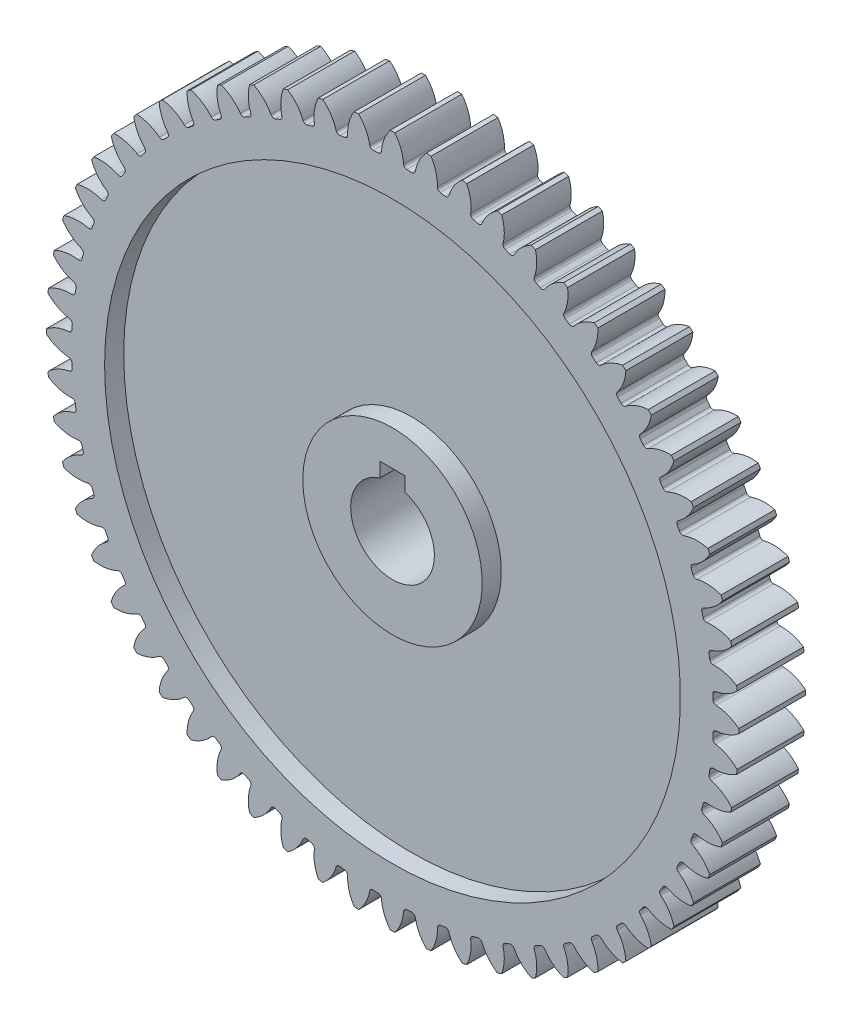
SolidWorks part; units mm, degrees
ref_plane "Front Plane" through (0, 0, 0) normal (0, 0, 1) x (1, 0, 0)
ref_plane "Top Plane" through (0, 0, 0) normal (0, 1, 0) x (1, 0, 0)
ref_plane "Right Plane" through (0, 0, 0) normal (1, 0, 0) x (0, 0, -1)
sketch "Sketch1" plane through (0, 0, 0) normal (1, 0, 0) x (0, 0, -1)
  line L0 (-7.112, 0) -> (-7.112, 32.8359)
  line L1 (-7.112, 32.8359) -> (-0.762, 32.8359)
  line L2 (-0.762, 32.8359) -> (-0.762, 8.509)
  line L3 (-0.762, 8.509) -> (7.112, 8.509)
  line L4 (7.112, 8.509) -> (7.112, 0)
  line L5 (7.112, 0) -> (-7.112, 0) construction
  line L6 (-7.112, 3.9687) -> (7.112, 3.9687)
  point P9 (-7.112, 27.305)
  dimension "OD" = 65.6717
  dimension "Face Width" = 6.35
  dimension "Hub Width" = 7.874
  dimension "Hub Diameter" = 17.018
  dimension "For Shaft Diameter" = 7.9375
  dimension "Overall Width" = 14.224
  dimension "Under Cut Diameter" = 54.61
sketch "Sketch2" plane through (0, 0, 0) normal (0, 0, 1) x (1, 0, 0)
  line L0 (-1.3192, 30.3985) -> (-0.432, 32.8359)
  line L1 (-0.432, 32.8359) -> (0.432, 32.8359)
  line L2 (0.432, 32.8359) -> (1.3192, 30.3985)
  line L3 (0, 32.8359) -> (0, 0) construction
  line L4 (0, 0) -> (-1.7185, 32.7908) construction
  line L5 (0, 0) -> (1.7185, 32.7908) construction
  line L6 (-4.4894, 30.0941) -> (-3.862, 32.6108)
  line L7 (-3.862, 32.6108) -> (-3.0026, 32.7011)
  line L8 (-3.0026, 32.7011) -> (-1.8656, 30.3698)
  line L9 (-3.4323, 32.656) -> (0, 0) construction
  line L11 (-0.432, 32.8359) -> (0, 32.8359) construction
  line L12 (-0.8312, 31.7391) -> (0.8312, 31.7391) construction
  circle A0 centre (0, 0) radius 31.75 construction
  circle A2 centre (0, 0) radius 32.8359
  circle A3 centre (0, 0) radius 30.4271
  arc A5 (-0.216, 32.8359) -> (-1.0661, 30.4084) centre (2.8289, 30.407) ccw
  arc A6 (1.0661, 30.4084) -> (0.216, 32.8359) centre (-2.8289, 30.407) ccw
  arc A7 (-2.1183, 30.3533) -> (-3.2174, 32.6786) centre (-5.9918, 29.9447) ccw
  arc A8 (-0.8312, 31.7391) -> (0.8312, 31.7391) centre (0, 0) cw
  point P3 (0, 31.75)
  point P5 (3.3188, 31.5761)
  point P6 (27.4963, -15.875)
  point P9 (6.6012, 31.0562)
  point P10 (9.8113, 30.196)
  point P11 (12.9139, 29.0051)
  point P12 (15.875, 27.4963)
  point P13 (18.6622, 25.6863)
  point P14 (21.2449, 23.5948)
  point P15 (23.5948, 21.2449)
  point P16 (25.6863, 18.6622)
  point P17 (27.4963, 15.875)
  point P18 (29.0051, 12.9139)
  point P19 (30.196, 9.8113)
  point P20 (31.0562, 6.6012)
  point P21 (31.5761, 3.3188)
  point P22 (31.75, 0)
  point P23 (31.5761, -3.3188)
  point P24 (31.0562, -6.6012)
  point P25 (30.196, -9.8113)
  point P26 (29.0051, -12.9139)
  point P27 (25.6863, -18.6622)
  point P28 (23.5948, -21.2449)
  point P29 (21.2449, -23.5948)
  point P30 (18.6622, -25.6863)
  point P31 (0, 0)
  point P55 (15.875, -27.4963)
  point P56 (12.9139, -29.0051)
  point P57 (9.8113, -30.196)
  point P58 (6.6012, -31.0562)
  point P59 (3.3188, -31.5761)
  point P61 (0, -31.75)
  point P62 (-3.3188, -31.5761)
  point P63 (-6.6012, -31.0562)
  point P64 (-9.8113, -30.196)
  point P65 (-12.9139, -29.0051)
  point P66 (-15.875, -27.4963)
  point P67 (-18.6622, -25.6863)
  point P68 (-21.2449, -23.5948)
  point P69 (-23.5948, -21.2449)
  point P70 (-25.6863, -18.6622)
  point P71 (-27.4963, -15.875)
  point P72 (-29.0051, -12.9139)
  point P73 (-30.196, -9.8113)
  point P74 (-31.0562, -6.6012)
  point P75 (-31.5761, -3.3188)
  point P76 (-31.75, 0)
  point P77 (-31.5761, 3.3188)
  point P78 (-31.0562, 6.6012)
  point P79 (-30.196, 9.8113)
  point P80 (-29.0051, 12.9139)
  point P81 (-27.4963, 15.875)
  point P82 (-25.6863, 18.6622)
  point P83 (-23.5948, 21.2449)
  point P84 (-21.2449, 23.5948)
  point P85 (-18.6622, 25.6863)
  point P86 (-15.875, 27.4963)
  point P87 (-12.9139, 29.0051)
  point P88 (-9.8113, 30.196)
  point P89 (-6.6012, 31.0562)
  point P90 (-3.3188, 31.5761)
  dimension "Gear Pitch Diameter" = 63.5
  dimension "Pressure Angle" = 20
  dimension "Addendum" = 1.0858
  dimension "Dedendum" = 1.3229
  dimension "D1" = 6
  dimension "D2" = 1.6624
  dimension "Number of Teeth" = 60
sketch "Sketch3" plane through (0, 0, 0) normal (1, 0, 0) x (0, 0, -1)
  line L0 (-7.112, 32.8359) -> (-0.762, 32.8359) construction
  line L1 (7.112, 8.509) -> (7.112, 0) construction
  line L2 (-0.762, 8.509) -> (7.112, 8.509) construction
  line L3 (-0.762, 32.8359) -> (-0.762, 8.509) construction
  line L4 (-7.112, 0) -> (-7.112, 32.8359) construction
  line L5 (-7.112, 3.9687) -> (7.112, 3.9687) construction
  line L6 (-7.112, 32.8359) -> (-0.762, 32.8359)
  line L7 (7.112, 8.509) -> (7.112, 3.9687)
  line L8 (-7.112, 8.509) -> (-5.2977, 8.509)
  line L9 (-0.762, 32.8359) -> (-0.762, 27.305)
  line L10 (-7.112, 3.9687) -> (-7.112, 8.509)
  line L11 (-7.112, 3.9687) -> (7.112, 3.9687)
  line L12 (-7.112, 27.305) -> (-5.2977, 27.305)
  line L13 (-5.2977, 27.305) -> (-5.2977, 8.509)
  line L14 (-0.762, 27.305) -> (-2.5763, 27.305)
  line L15 (-2.5763, 27.305) -> (-2.5763, 8.509)
  line L16 (-2.5763, 8.509) -> (7.112, 8.509)
  line L17 (-7.112, 27.305) -> (-7.112, 32.8359)
  dimension "D1" = 1.8143
revolve "Revolve1" add sketch "Sketch3" angle 360 about L5
sketch "Sketch4" plane through (0, 0, 7.112) normal (0, 0, 1) x (1, 0, 0)
  arc A1 (-0.216, 32.8358) -> (-1.0661, 30.4084) centre (2.8289, 30.407) ccw construction
  arc A2 (-2.1183, 30.3533) -> (-3.2174, 32.6786) centre (-5.9918, 29.9447) ccw construction
  arc A3 (-0.2166, 32.8351) -> (-1.0558, 30.6908) centre (2.8289, 30.407) ccw
  arc A4 (-2.1581, 30.633) -> (-3.2168, 32.6779) centre (-5.9918, 29.9447) ccw
  circle A5 centre (0, 0) radius 32.8359 construction
  arc A6 (-0.2166, 32.8351) -> (-3.2168, 32.6779) centre (0, 0) ccw
  circle A7 centre (0, 0) radius 30.4271 construction
  arc A8 (-1.3582, 30.3968) -> (-1.8265, 30.3722) centre (0, 0) ccw
  arc A9 (-2.1581, 30.633) -> (-1.8265, 30.3722) centre (-1.8456, 30.6891) ccw
  arc A10 (-1.3582, 30.3968) -> (-1.0558, 30.6908) centre (-1.3724, 30.7139) ccw
  dimension "D1" = 0.3175
extrude "Cut-Extrude1" cut sketch "Sketch4" against normal through all both and the other way through all
pattern_circular "CirPattern1" count 60 over 360 about axis through (0, 0, -7.112) along (0, 0, -1) of "Cut-Extrude1"
sketch "Sketch5" plane through (0, 0, -7.112) normal (0, 0, -1) x (-1, 0, 0)
  line L1 (-1.1906, 5.1594) -> (1.1906, 5.1594)
  line L2 (-1.1906, 5.1594) -> (-1.1906, 2.7781)
  line L3 (-1.1906, 2.7781) -> (1.1906, 2.7781)
  line L4 (1.1906, 5.1594) -> (1.1906, 2.7781)
  line L5 (-1.1906, 5.1594) -> (1.1906, 2.7781) construction
  line L6 (-1.1906, 2.7781) -> (1.1906, 5.1594) construction
  circle A0 centre (0, 0) radius 3.9687 construction
  point P0 (0, 3.9687)
  dimension "D1" = 2.3813
extrude "Cut-Extrude2" cut sketch "Sketch5" against normal through all
equation "\"Dedendum@Sketch2\" = 1.25 /  ( \"Number of Teeth@Sketch2\" / \"Gear Pitch Diameter@Sketch2\" ) "
equation "\"D1@Sketch2\"=360/\"Number of Teeth@Sketch2\""
equation "\"D1@Sketch4\"=.3/(\"Number of Teeth@Sketch2\"/\"Gear Pitch Diameter@Sketch2\")"
equation "\"D1@CirPattern1\"=\"Number of Teeth@Sketch2\""
equation "\"D2@Sketch2\"=1.5708/(\"Number of Teeth@Sketch2\"/\"Gear Pitch Diameter@Sketch2\")"
equation "\"D1@Sketch3\"=\"Face Width@Sketch1\"/3.5"
